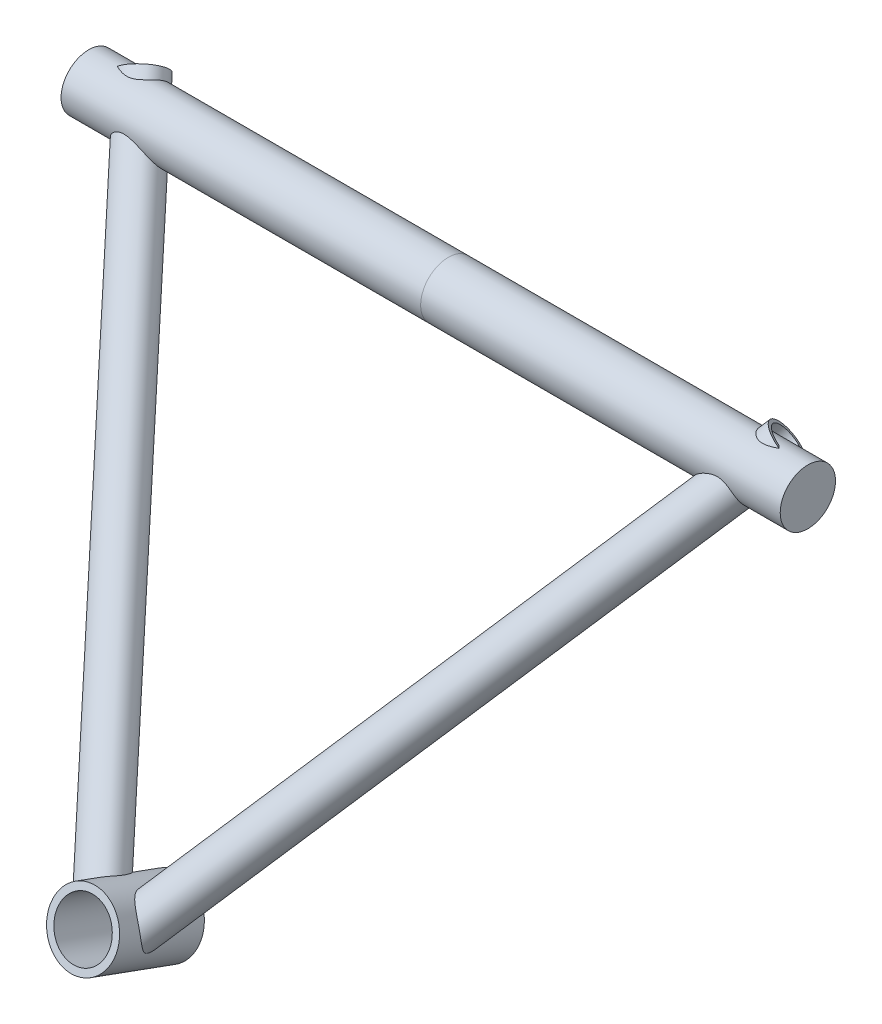
SolidWorks part; units mm, degrees
material "AISI 4130 Steel, normalized at 870C"
ref_plane "Front Plane" through (0, 0, 0) normal (0, 0, 1) x (1, 0, 0)
ref_plane "Top Plane" through (0, 0, 0) normal (0, 1, 0) x (1, 0, 0)
ref_plane "Right Plane" through (0, 0, 0) normal (1, 0, 0) x (0, 0, -1)
sketch "Sketch3" plane through (0, 0, 0) normal (0, 1, 0) x (1, 0, 0)
  line L0 (-5.08, -6.35) -> (5.08, -6.35) construction
  line L2 (0, -88.2205) -> (0, 88.2205) construction
  line L3 (5.08, 0) -> (-5.08, 0) construction
  dimension "D1" = 5.08
  dimension "D2" = 10.16
  dimension "D3" = 6.35
  dimension "D4" = 10.16
  dimension "D5" = 5.08
ref_plane "Plane1" through (0, 3.1441, 3.6169) normal (0, 0.6561, 0.7547) x (1, 0, 0)
ref_plane "Plane3" through (0, 0, 0) normal (0, 0.342, 0.9397) x (-1, 0, 0)
sketch "Sketch1" plane through (0, 0, 0) normal (0, 0.342, 0.9397) x (1, 0, 0)
  circle A0 centre (0, 0) radius 15.875
  dimension "D1" = 31.75
extrude "Boss-Extrude1" add sketch "Sketch1" along normal mid plane 41.402 contours A0
sketch "Sketch4" plane through (0, 3.1441, 3.6169) normal (0, 0.6561, 0.7547) x (1, 0, 0)
  line L0 (-5.08, -4.166) -> (-147.955, 243.3008)
  line L2 (0, -102.3339) -> (0, 102.3339) construction
  dimension "D2" = 30
  dimension "D3" = 285.75
sweep "Sweep1" add path "Sketch4" circular profile diameter 19.05 parameters "D3"=19.05
sketch "Sketch15" plane through (0, 3.1441, 3.6169) normal (0, 0.6561, 0.7547) x (1, 0, 0)
  line L0 (5.08, -4.166) -> (147.955, 243.3008)
  line L1 (0, -102.3339) -> (0, 102.3339) construction
  dimension "D1" = 285.75
  dimension "D2" = 30
sweep "Sweep2" add path "Sketch15" circular profile diameter 19.05 parameters "D3"=19.05
sketch "Sketch36" plane through (-142.3411, 186.0676, -161.7461) normal (-0.5, 0.6536, -0.5682) x (0.866, 0.3839, -0.3204)
  circle A0 centre (-6.434, -4.8572) radius 7.9375
  dimension "D1" = 15.875
extrude "Cut-Extrude2" cut sketch "Sketch36" against normal up to surface (305.3325 mm away) up to face at (14.707, 3.1915, -8.7057)
sketch "Sketch37" plane through (142.3411, 186.0676, -161.7461) normal (0.5, 0.6536, -0.5682) x (0.866, -0.3839, 0.3204)
  circle A0 centre (6.434, -4.8572) radius 7.9375
  dimension "D1" = 15.875
extrude "Cut-Extrude3" cut sketch "Sketch37" against normal up to surface (272.9927 mm away) up to face at (1.1745, -13.9472, 7.9687)
sketch "Sketch77" plane through (0, 7.0802, 19.4526) normal (0, 0.342, 0.9397) x (1, 0, 0)
  circle A1 centre (0, 0) radius 15.875
extrude "Boss-Extrude2" add sketch "Sketch77" against normal up to surface (41.402 mm away) up to face at (0, -21.9978, -14.023)
sketch "Sketch2" plane through (0, -7.0802, -19.4526) normal (0, -0.342, -0.9397) x (-1, 0, 0)
  circle A0 centre (0, 0) radius 12.7
  dimension "D1" = 25.4
extrude "Cut-Extrude1" cut sketch "Sketch2" against normal up to next
ref_plane "Plane2" through (0, 0, -127) normal (0, 0, 1) x (1, 0, 0)
ref_plane "Plane4" through (0, 177.8, 0) normal (0, 1, 0) x (1, 0, 0)
sketch "Sketch40" plane through (-106.934, 0, -127) normal (0, 0, 1) x (1, 0, 0)
  line L2 (106.934, -103.7978) -> (106.934, 103.7978) construction
  line L3 (100.2024, 162.3048) -> (-63.6638, 149.8608)
  line L4 (113.6656, 162.3048) -> (277.5318, 149.8608)
  arc A0 (100.2024, 162.3048) -> (113.6656, 162.3048) centre (106.934, 73.66) cw
  point P0 (106.934, 162.56)
  point P4 (0, 0)
  point P7 (106.934, 162.56)
  point P9 (0, 0)
  point P12 (0, 0)
  point P13 (0, 0)
  point P14 (0, 0)
  point P15 (0, 0)
  dimension "D1" = 164.338
  dimension "D3" = 88.9
  dimension "D2" = 164.338
  dimension "D4" = 4.75
sweep "Sweep3" [suppressed] add path "Sketch40" circular profile diameter 25.4 parameters "D3"=25.4
sketch "Sketch118" plane through (0, 177.8, 0) normal (0, 1, 0) x (1, 0, 0)
  line L0 (0, 148.2378) -> (-165.1, 148.2378)
  line L1 (0, 148.2378) -> (165.1, 148.2378)
  dimension "D1" = 165.1
  dimension "D2" = 165.1
sweep "Sweep4" add path "Sketch118" circular profile diameter 25.4 parameters "D3"=25.4
